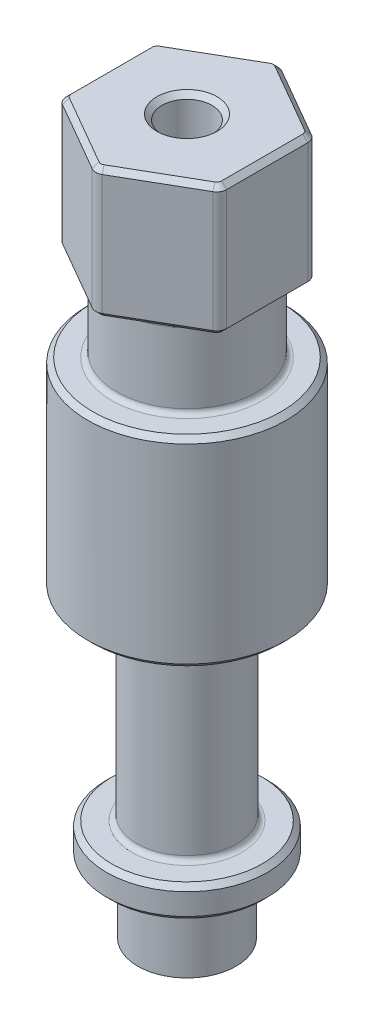
SolidWorks part; units mm, degrees
material "AISI 304"
ref_plane "Front Plane" through (0, 0, 0) normal (0, 0, 1) x (1, 0, 0)
ref_plane "Top Plane" through (0, 0, 0) normal (0, 1, 0) x (1, 0, 0)
ref_plane "Right Plane" through (0, 0, 0) normal (1, 0, 0) x (0, 0, -1)
sketch "Sketch1" plane through (0, 0, 0) normal (0, 0, 1) x (1, 0, 0)
  line L0 (0, -485.8568) -> (0, 23806.981) construction
  line L1 (-485.8568, 0) -> (23806.981, 0) construction
  line L2 (0, 29.07) -> (3.5, 29.07)
  line L3 (3.5, 29.07) -> (3.5, 25.07)
  line L4 (3.5, 25.07) -> (4.95, 25.07)
  line L5 (4.95, 25.07) -> (4.95, 15.07)
  line L6 (4.95, 15.07) -> (2.5, 15.07)
  line L7 (2.5, 15.07) -> (2.5, 5.07)
  line L8 (2.5, 5.07) -> (4, 5.07)
  line L9 (4, 5.07) -> (4, 3.5)
  line L10 (4, 3.5) -> (2.45, 3.5)
  line L11 (2.45, 3.5) -> (2.45, 0)
  line L12 (2.45, 0) -> (0, 0)
  line L13 (0, 0) -> (0, 29.07)
  dimension "D1" = 7
  dimension "D2" = 9.9
  dimension "D3" = 5
  dimension "D4" = 4.9
  dimension "D5" = 8
  dimension "D6" = 1.57
  dimension "D7" = 3.5
  dimension "D8" = 10
  dimension "D9" = 10
  dimension "D10" = 4
revolve "Revolve1" add sketch "Sketch1" angle 360 about L0
chamfer "Chamfer1" distance 0.25 angle 45 4 edges at (4.95, 15.07, 0) (4.95, 25.07, 0) (4, 5.07, 0) (4, 3.5, 0)
fillet "Fillet1" radius 0.25 4 edges at (3.5, 25.07, 0) (2.5, 15.07, 0) (2.5, 5.07, 0) (2.45, 3.5, 0)
sketch "Sketch2" plane through (0, 29.07, 0) normal (0, 1, 0) x (1, 0, 0)
  line L0 (0, -1000) -> (0, 49000) construction
  line L1 (4, 2.3094) -> (0, 4.6188)
  line L2 (0, 4.6188) -> (-4, 2.3094)
  line L3 (-4, 2.3094) -> (-4, -2.3094)
  line L4 (-4, -2.3094) -> (0, -4.6188)
  line L5 (0, -4.6188) -> (4, -2.3094)
  line L6 (4, -2.3094) -> (4, 2.3094)
  circle A0 centre (0, 0) radius 4 construction
  point P1 (-0.2027, 4.6956)
  dimension "D1" = 8
extrude "Boss-Extrude1" add sketch "Sketch2" along normal blind 6.5
sketch "Sketch3" plane through (0, 35.57, 0) normal (0, 1, 0) x (1, 0, 0)
  circle A0 centre (0, 0) radius 1.25
  dimension "D1" = 2.5
extrude "Cut-Extrude1" cut sketch "Sketch3" against normal up to next
fillet "Fillet2" radius 0.5 6 edges at (0, 32.32, -4.6188) (-4, 32.32, -2.3094) (4, 32.32, -2.3094) (4, 32.32, 2.3094) (-4, 32.32, 2.3094) (0, 32.32, 4.6188)
fillet "Fillet3" radius 0.25 1 edges at (3.5, 29.07, 0)
chamfer "Chamfer2" distance 0.25 angle 45 25 edges at (-3.933, 29.07, -2.2707) (-4, 29.07, 0) (-3.933, 29.07, 2.2707) (-2, 29.07, 3.4641) (0, 29.07, 4.5415) (2, 29.07, 3.4641) (3.933, 29.07, 2.2707) (4, 29.07, 0) (3.933, 29.07, -2.2707) (2, 29.07, -3.4641) (0, 29.07, -4.5415) (-2, 29.07, -3.4641) (3.933, 35.57, -2.2707) (4, 35.57, 0) (3.933, 35.57, 2.2707) (2, 35.57, 3.4641) (0, 35.57, 4.5415) (-2, 35.57, 3.4641) (-3.933, 35.57, 2.2707) (-4, 35.57, 0) (-3.933, 35.57, -2.2707) (-2, 35.57, -3.4641) (0, 35.57, -4.5415) (2, 35.57, -3.4641) (-1.25, 35.57, 0)
